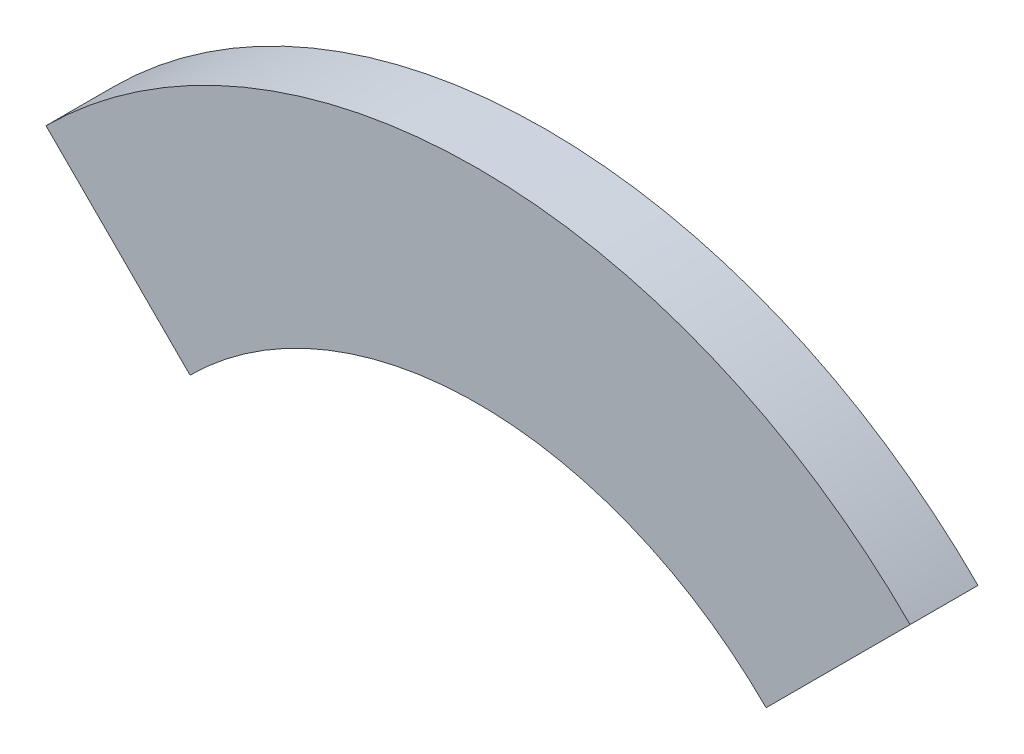
SolidWorks part; units mm, degrees
ref_plane "Front Plane" through (0, 0, 0) normal (0, 0, 1) x (1, 0, 0)
ref_plane "Top Plane" through (0, 0, 0) normal (0, 1, 0) x (1, 0, 0)
ref_plane "Right Plane" through (0, 0, 0) normal (1, 0, 0) x (0, 0, -1)
sketch "Sketch1" plane through (0, 0, 0) normal (0, 0, 1) x (1, 0, 0)
  line L0 (-127, 127) -> (0, 0) construction
  line L1 (0, 0) -> (127, 127) construction
  line L2 (0, 0) -> (-107.7631, 107.7631) construction
  line L3 (0, 0) -> (-161.6446, 161.6446) construction
  arc A0 (-127, 127) -> (127, 127) centre (0, 0) cw
  point P3 (0, 179.6051)
  dimension "D1" = 254
  dimension "D2" = 90
  dimension "D3" = 228.6
  dimension "D4" = 152.4
ref_plane "Plane1" through (0, 0, 0) normal (0, 0, 1) x (1, 0, 0)
ref_plane "Plane2" through (0, 0, 0) normal (-0.7071, -0.7071, 0) x (0.7071, -0.7071, 0)
sketch "Sketch2" plane through (0, 0, 0) normal (-0.7071, -0.7071, 0) x (0.7071, -0.7071, 0)
  line L0 (-179.6051, 0) -> (0, 0) construction
  line L1 (-228.6, 12.7) -> (-152.4, 12.7)
  line L2 (-228.6, 12.7) -> (-228.6, -12.7)
  line L3 (-228.6, -12.7) -> (-152.4, -12.7)
  line L4 (-152.4, 12.7) -> (-152.4, -12.7)
  line L7 (0, 0) -> (-179.6051, 0) construction
  point P0 (-179.6051, 0)
  point P9 (-152.4, 0)
  dimension "D3" = 25.4
sweep "Sweep1" add profiles "Sketch2" path "Sketch1"
ref_plane "Plane3" through (0, 127, 0) normal (0, -1, 0) x (-1, 0, 0)
sketch "Sketch3" plane through (0, 127, 0) normal (0, -1, 0) x (-1, 0, 0)
  line L0 (-127, 30.1437) -> (-127, -17.2956)
  line L1 (127, 30.1437) -> (127, -17.2956)
equation "\"theta\"= pi / 2 * 180 / pi"
equation "\"a\" = 6"
equation "\"b\" = 1"
equation "\"c\" = 9"
equation "\"D2@Sketch1\"=\"theta\""
equation "\"D3@Sketch2\"=\"b\""
equation "\"D3@Sketch1\"=\"c\""
equation "\"D4@Sketch1\"=\"a\""
